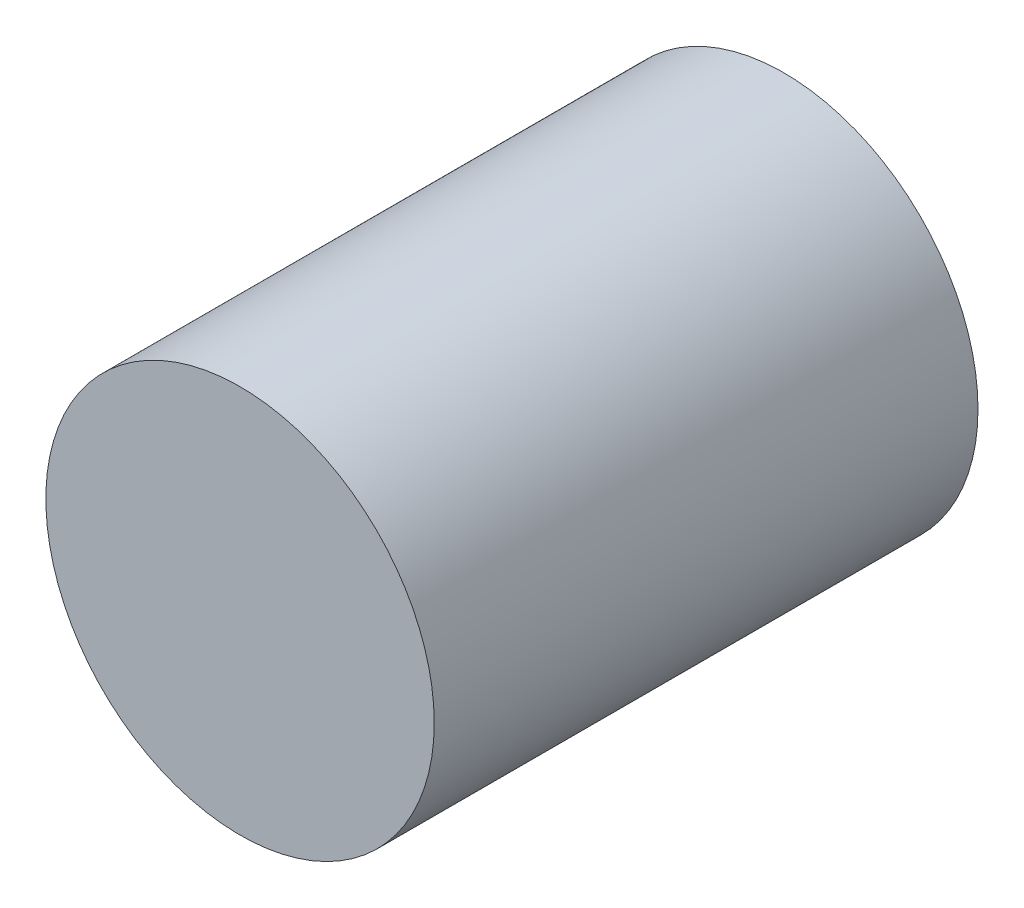
SolidWorks part; units mm, degrees
ref_plane "Front Plane" through (0, 0, 0) normal (0, 0, 1) x (1, 0, 0)
ref_plane "Top Plane" through (0, 0, 0) normal (0, 1, 0) x (1, 0, 0)
ref_plane "Right Plane" through (0, 0, 0) normal (1, 0, 0) x (0, 0, -1)
sketch "Sketch1" plane through (0, 0, 0) normal (0, 0, 1) x (1, 0, 0)
  circle A0 centre (0, 0) radius 10
  dimension "D1" = 20
extrude "Boss-Extrude1" add sketch "Sketch1" along normal blind 28
